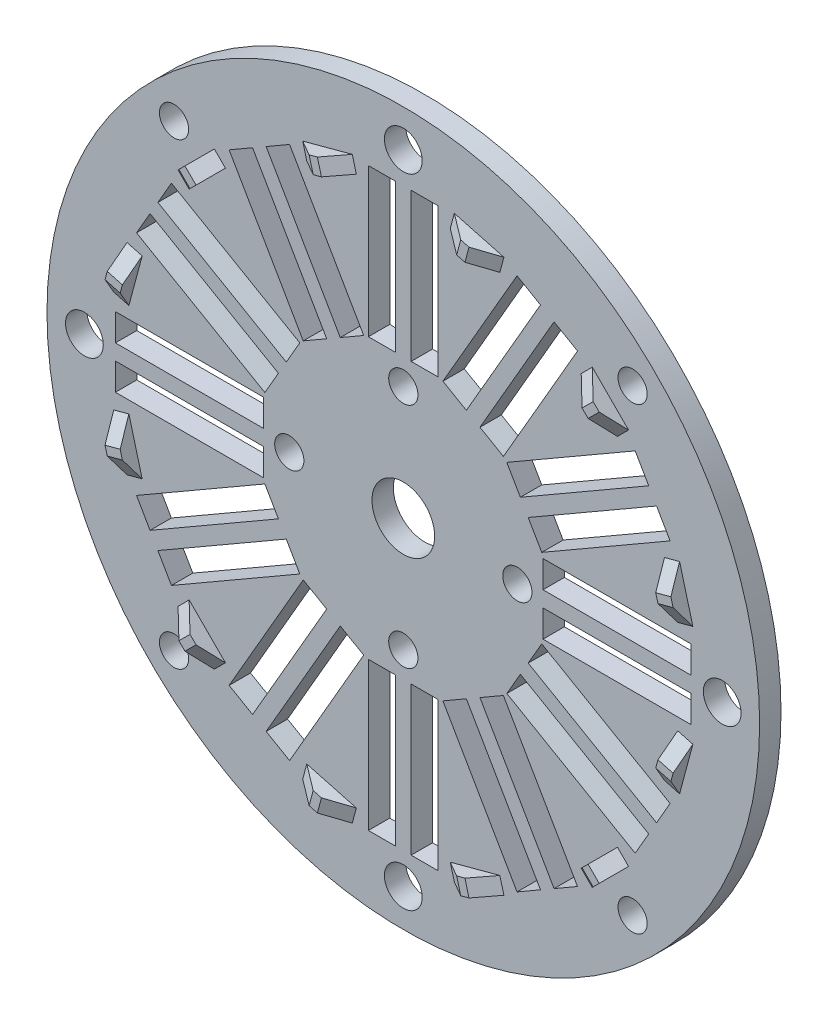
SolidWorks part; units mm, degrees
ref_plane "Alzado" through (0, 0, 0) normal (1, 0, 0) x (0, 1, 0)
ref_plane "Planta" through (0, 0, 0) normal (0, 0, 1) x (0, 1, 0)
ref_plane "Vista lateral" through (0, 0, 0) normal (0, 1, 0) x (-1, 0, 0)
sketch "Croquis1" plane through (0, 0, 0) normal (0, 0, 1) x (0, 1, 0)
  circle A0 centre (0, 0) radius 50
  dimension "D1" = 100
extrude "Saliente-Extruir1" add sketch "Croquis1" along normal blind 3
sketch "Croquis2" plane through (0, 0, 3) normal (0, 0, 1) x (1, 0, 0)
  line L102 (15.9565, 37.4374) -> (5.5565, 19.4241)
  line L103 (-4.9, 40.4) -> (4.9, 40.4)
  line L104 (-4.9, 40.4) -> (-4.9, 19.6)
  line L105 (-4.9, 19.6) -> (4.9, 19.6)
  line L106 (4.9, 40.4) -> (4.9, 19.6)
  line L107 (-4.9, 40.4) -> (4.9, 19.6) construction
  line L108 (-4.9, 19.6) -> (4.9, 40.4) construction
  line L109 (15.9565, 37.4374) -> (24.4435, 32.5374)
  line L110 (24.4435, 32.5374) -> (14.0435, 14.5241)
  line L111 (5.5565, 19.4241) -> (14.0435, 14.5241)
  line L112 (32.5374, 24.4435) -> (14.5241, 14.0435)
  line L113 (32.5374, 24.4435) -> (37.4374, 15.9565)
  line L114 (37.4374, 15.9565) -> (19.4241, 5.5565)
  line L115 (14.5241, 14.0435) -> (19.4241, 5.5565)
  line L116 (40.4, 4.9) -> (19.6, 4.9)
  line L117 (40.4, 4.9) -> (40.4, -4.9)
  line L118 (40.4, -4.9) -> (19.6, -4.9)
  line L119 (19.6, 4.9) -> (19.6, -4.9)
  line L120 (37.4374, -15.9565) -> (19.4241, -5.5565)
  line L121 (37.4374, -15.9565) -> (32.5374, -24.4435)
  line L122 (32.5374, -24.4435) -> (14.5241, -14.0435)
  line L123 (19.4241, -5.5565) -> (14.5241, -14.0435)
  line L124 (24.4435, -32.5374) -> (14.0435, -14.5241)
  line L125 (24.4435, -32.5374) -> (15.9565, -37.4374)
  line L126 (15.9565, -37.4374) -> (5.5565, -19.4241)
  line L127 (14.0435, -14.5241) -> (5.5565, -19.4241)
  line L128 (4.9, -40.4) -> (4.9, -19.6)
  line L129 (4.9, -40.4) -> (-4.9, -40.4)
  line L130 (-4.9, -40.4) -> (-4.9, -19.6)
  line L131 (4.9, -19.6) -> (-4.9, -19.6)
  line L132 (-15.9565, -37.4374) -> (-5.5565, -19.4241)
  line L133 (-15.9565, -37.4374) -> (-24.4435, -32.5374)
  line L135 (-24.4435, -32.5374) -> (-14.0435, -14.5241)
  line L136 (-5.5565, -19.4241) -> (-14.0435, -14.5241)
  line L180 (-32.5374, -24.4435) -> (-14.5241, -14.0435)
  line L181 (-32.5374, -24.4435) -> (-37.4374, -15.9565)
  line L182 (-37.4374, -15.9565) -> (-19.4241, -5.5565)
  line L183 (-14.5241, -14.0435) -> (-19.4241, -5.5565)
  line L184 (-40.4, -4.9) -> (-19.6, -4.9)
  line L185 (-40.4, -4.9) -> (-40.4, 4.9)
  line L186 (-40.4, 4.9) -> (-19.6, 4.9)
  line L187 (-19.6, -4.9) -> (-19.6, 4.9)
  line L188 (-37.4374, 15.9565) -> (-19.4241, 5.5565)
  line L189 (-37.4374, 15.9565) -> (-32.5374, 24.4435)
  line L190 (-32.5374, 24.4435) -> (-14.5241, 14.0435)
  line L191 (-19.4241, 5.5565) -> (-14.5241, 14.0435)
  line L192 (-24.4435, 32.5374) -> (-14.0435, 14.5241)
  line L193 (-24.4435, 32.5374) -> (-15.9565, 37.4374)
  line L194 (-15.9565, 37.4374) -> (-5.5565, 19.4241)
  line L195 (-14.0435, 14.5241) -> (-5.5565, 19.4241)
  point P0 (0, 30)
  point P51 (0, 0)
  dimension "D1" = 20.8
  dimension "D2" = 9.8
  dimension "D3" = 0
  dimension "D4" = 30
  dimension "D5" = 12
extrude "Cortar-Extruir1" cut sketch "Croquis2" against normal through all
sketch "Croquis3" plane through (0, 0, 3) normal (0, 0, 1) x (1, 0, 0)
  line L5 (19.2474, 35.5374) -> (8.8474, 17.5241)
  line L6 (-1.1, 40.4) -> (1.1, 40.4)
  line L51 (-1.1, 40.4) -> (-1.1, 19.6)
  line L52 (-1.1, 19.6) -> (1.1, 19.6)
  line L53 (1.1, 40.4) -> (1.1, 19.6)
  line L54 (-1.1, 40.4) -> (1.1, 19.6) construction
  line L55 (-1.1, 19.6) -> (1.1, 40.4) construction
  line L56 (19.2474, 35.5374) -> (21.1526, 34.4374)
  line L57 (21.1526, 34.4374) -> (10.7526, 16.4241)
  line L58 (8.8474, 17.5241) -> (10.7526, 16.4241)
  line L59 (34.4374, 21.1526) -> (16.4241, 10.7526)
  line L60 (34.4374, 21.1526) -> (35.5374, 19.2474)
  line L61 (35.5374, 19.2474) -> (17.5241, 8.8474)
  line L62 (16.4241, 10.7526) -> (17.5241, 8.8474)
  line L63 (40.4, 1.1) -> (19.6, 1.1)
  line L64 (40.4, 1.1) -> (40.4, -1.1)
  line L65 (40.4, -1.1) -> (19.6, -1.1)
  line L66 (19.6, 1.1) -> (19.6, -1.1)
  line L67 (35.5374, -19.2474) -> (17.5241, -8.8474)
  line L68 (35.5374, -19.2474) -> (34.4374, -21.1526)
  line L69 (34.4374, -21.1526) -> (16.4241, -10.7526)
  line L70 (17.5241, -8.8474) -> (16.4241, -10.7526)
  line L71 (21.1526, -34.4374) -> (10.7526, -16.4241)
  line L72 (21.1526, -34.4374) -> (19.2474, -35.5374)
  line L73 (19.2474, -35.5374) -> (8.8474, -17.5241)
  line L74 (10.7526, -16.4241) -> (8.8474, -17.5241)
  line L75 (1.1, -40.4) -> (1.1, -19.6)
  line L76 (1.1, -40.4) -> (-1.1, -40.4)
  line L77 (-1.1, -40.4) -> (-1.1, -19.6)
  line L78 (1.1, -19.6) -> (-1.1, -19.6)
  line L79 (-19.2474, -35.5374) -> (-8.8474, -17.5241)
  line L80 (-19.2474, -35.5374) -> (-21.1526, -34.4374)
  line L81 (-21.1526, -34.4374) -> (-10.7526, -16.4241)
  line L82 (-8.8474, -17.5241) -> (-10.7526, -16.4241)
  line L83 (-34.4374, -21.1526) -> (-16.4241, -10.7526)
  line L84 (-34.4374, -21.1526) -> (-35.5374, -19.2474)
  line L85 (-35.5374, -19.2474) -> (-17.5241, -8.8474)
  line L86 (-16.4241, -10.7526) -> (-17.5241, -8.8474)
  line L87 (-40.4, -1.1) -> (-19.6, -1.1)
  line L88 (-40.4, -1.1) -> (-40.4, 1.1)
  line L89 (-40.4, 1.1) -> (-19.6, 1.1)
  line L90 (-19.6, -1.1) -> (-19.6, 1.1)
  line L91 (-35.5374, 19.2474) -> (-17.5241, 8.8474)
  line L92 (-35.5374, 19.2474) -> (-34.4374, 21.1526)
  line L93 (-34.4374, 21.1526) -> (-16.4241, 10.7526)
  line L94 (-17.5241, 8.8474) -> (-16.4241, 10.7526)
  line L95 (-21.1526, 34.4374) -> (-10.7526, 16.4241)
  line L96 (-21.1526, 34.4374) -> (-19.2474, 35.5374)
  line L97 (-19.2474, 35.5374) -> (-8.8474, 17.5241)
  line L98 (-10.7526, 16.4241) -> (-8.8474, 17.5241)
  point P0 (0, 30)
  point P7 (15, 25.9808)
  point P13 (25.9808, 15)
  point P18 (30, 0)
  point P23 (25.9808, -15)
  point P28 (15, -25.9808)
  point P33 (0, -30)
  point P38 (-15, -25.9808)
  point P43 (-25.9808, -15)
  point P48 (-30, 0)
  point P53 (-25.9808, 15)
  point P59 (-15, 25.9808)
  point P64 (0, 0)
  dimension "D1" = 30
  dimension "D2" = 20.8
  dimension "D3" = 2.2
  dimension "D4" = 12
extrude "Saliente-Extruir2" add sketch "Croquis3" against normal blind 3
sketch "Croquis5" plane through (0, 0, 3) normal (0, 0, 1) x (1, 0, 0)
  circle A0 centre (0, 0) radius 4.4
  circle A1 centre (0, 44.75) radius 2.65
  circle A2 centre (44.75, 0) radius 2.65
  circle A3 centre (0, -44.75) radius 2.65
  circle A4 centre (-44.75, 0) radius 2.65
  point P19 (0, 0)
  dimension "D2" = 8.8
  dimension "D3" = 5.3
  dimension "D5" = 5.3
  dimension "D6" = 5.3
  dimension "D7" = 5.3
  dimension "D1" = 44.75
  dimension "D4" = 4
extrude "Cortar-Extruir3" cut sketch "Croquis5" against normal blind 10
sketch "Croquis6" plane through (0, 0, 3) normal (0, 0, 1) x (1, 0, 0)
  line L0 (0, 0) -> (28.2843, 28.2843) construction
  line L6 (26.5165, 31.6077) -> (31.6077, 26.5165)
  line L7 (26.5165, 31.6077) -> (24.9609, 30.052)
  line L52 (24.9609, 30.052) -> (30.052, 24.9609)
  line L53 (31.6077, 26.5165) -> (30.052, 24.9609)
  line L54 (26.5165, 31.6077) -> (30.052, 24.9609) construction
  line L55 (24.9609, 30.052) -> (31.6077, 26.5165) construction
  line L56 (38.7678, 14.1148) -> (36.6428, 13.5454)
  line L57 (38.7678, 14.1148) -> (40.6313, 7.1601)
  line L58 (40.6313, 7.1601) -> (38.5063, 6.5907)
  line L59 (36.6428, 13.5454) -> (38.5063, 6.5907)
  line L60 (36.6428, 13.5454) -> (40.6313, 7.1601) construction
  line L61 (38.7678, 14.1148) -> (38.5063, 6.5907) construction
  line L62 (40.6313, -7.1601) -> (38.5063, -6.5907)
  line L63 (40.6313, -7.1601) -> (38.7678, -14.1148)
  line L64 (38.7678, -14.1148) -> (36.6428, -13.5454)
  line L65 (38.5063, -6.5907) -> (36.6428, -13.5454)
  line L66 (38.5063, -6.5907) -> (38.7678, -14.1148) construction
  line L67 (40.6313, -7.1601) -> (36.6428, -13.5454) construction
  line L68 (31.6077, -26.5165) -> (30.052, -24.9609)
  line L69 (31.6077, -26.5165) -> (26.5165, -31.6077)
  line L70 (26.5165, -31.6077) -> (24.9609, -30.052)
  line L71 (30.052, -24.9609) -> (24.9609, -30.052)
  line L72 (30.052, -24.9609) -> (26.5165, -31.6077) construction
  line L73 (31.6077, -26.5165) -> (24.9609, -30.052) construction
  line L74 (14.1148, -38.7678) -> (13.5454, -36.6428)
  line L75 (14.1148, -38.7678) -> (7.1601, -40.6313)
  line L76 (7.1601, -40.6313) -> (6.5907, -38.5063)
  line L77 (13.5454, -36.6428) -> (6.5907, -38.5063)
  line L78 (13.5454, -36.6428) -> (7.1601, -40.6313) construction
  line L79 (14.1148, -38.7678) -> (6.5907, -38.5063) construction
  line L80 (-7.1601, -40.6313) -> (-6.5907, -38.5063)
  line L81 (-7.1601, -40.6313) -> (-14.1148, -38.7678)
  line L82 (-14.1148, -38.7678) -> (-13.5454, -36.6428)
  line L83 (-6.5907, -38.5063) -> (-13.5454, -36.6428)
  line L84 (-6.5907, -38.5063) -> (-14.1148, -38.7678) construction
  line L85 (-7.1601, -40.6313) -> (-13.5454, -36.6428) construction
  line L86 (-26.5165, -31.6077) -> (-24.9609, -30.052)
  line L87 (-26.5165, -31.6077) -> (-31.6077, -26.5165)
  line L88 (-31.6077, -26.5165) -> (-30.052, -24.9609)
  line L89 (-24.9609, -30.052) -> (-30.052, -24.9609)
  line L90 (-24.9609, -30.052) -> (-31.6077, -26.5165) construction
  line L91 (-26.5165, -31.6077) -> (-30.052, -24.9609) construction
  line L92 (-38.7678, -14.1148) -> (-36.6428, -13.5454)
  line L93 (-38.7678, -14.1148) -> (-40.6313, -7.1601)
  line L94 (-40.6313, -7.1601) -> (-38.5063, -6.5907)
  line L95 (-36.6428, -13.5454) -> (-38.5063, -6.5907)
  line L96 (-36.6428, -13.5454) -> (-40.6313, -7.1601) construction
  line L97 (-38.7678, -14.1148) -> (-38.5063, -6.5907) construction
  line L98 (-40.6313, 7.1601) -> (-38.5063, 6.5907)
  line L99 (-40.6313, 7.1601) -> (-38.7678, 14.1148)
  line L100 (-38.7678, 14.1148) -> (-36.6428, 13.5454)
  line L101 (-38.5063, 6.5907) -> (-36.6428, 13.5454)
  line L102 (-38.5063, 6.5907) -> (-38.7678, 14.1148) construction
  line L103 (-40.6313, 7.1601) -> (-36.6428, 13.5454) construction
  line L104 (-31.6077, 26.5165) -> (-30.052, 24.9609)
  line L105 (-31.6077, 26.5165) -> (-26.5165, 31.6077)
  line L106 (-26.5165, 31.6077) -> (-24.9609, 30.052)
  line L107 (-30.052, 24.9609) -> (-24.9609, 30.052)
  line L108 (-30.052, 24.9609) -> (-26.5165, 31.6077) construction
  line L109 (-31.6077, 26.5165) -> (-24.9609, 30.052) construction
  line L110 (-14.1148, 38.7678) -> (-13.5454, 36.6428)
  line L111 (-14.1148, 38.7678) -> (-7.1601, 40.6313)
  line L112 (-7.1601, 40.6313) -> (-6.5907, 38.5063)
  line L113 (-13.5454, 36.6428) -> (-6.5907, 38.5063)
  line L114 (-13.5454, 36.6428) -> (-7.1601, 40.6313) construction
  line L115 (-14.1148, 38.7678) -> (-6.5907, 38.5063) construction
  line L116 (7.1601, 40.6313) -> (6.5907, 38.5063)
  line L117 (7.1601, 40.6313) -> (14.1148, 38.7678)
  line L118 (14.1148, 38.7678) -> (13.5454, 36.6428)
  line L119 (6.5907, 38.5063) -> (13.5454, 36.6428)
  line L120 (6.5907, 38.5063) -> (14.1148, 38.7678) construction
  line L121 (7.1601, 40.6313) -> (13.5454, 36.6428) construction
  point P0 (28.2843, 28.2843)
  point P53 (0, 0)
  dimension "D1" = 7.2
  dimension "D2" = 2.2
extrude "Saliente-Extruir3" add sketch "Croquis6" along normal blind 2
chamfer "Chaflán1" distance 2 distance2 3 12 edges at (6.8754, -39.5688, 5) (-30.8299, -25.7387, 5) (-13.8301, -37.7053, 5) (25.7387, -30.8299, 5) (37.7053, -13.8301, 5) (39.5688, 6.8754, 5) (-39.5688, -6.8754, 5) (-37.7053, 13.8301, 5) (-25.7387, 30.8299, 5) (-6.8754, 39.5688, 5) (13.8301, 37.7053, 5) (30.8299, 25.7387, 5) first distance on face at (6.8754, -39.5688, 4) first distance on face at (-30.8299, -25.7387, 4) first distance on face at (-13.8301, -37.7053, 4) first distance on face at (25.7387, -30.8299, 4) first distance on face at (37.7053, -13.8301, 4) first distance on face at (39.5688, 6.8754, 4) first distance on face at (-39.5688, -6.8754, 4) first distance on face at (-37.7053, 13.8301, 4) first distance on face at (-25.7387, 30.8299, 4) first distance on face at (-6.8754, 39.5688, 4) first distance on face at (13.8301, 37.7053, 4) first distance on face at (30.8299, 25.7387, 4)
chamfer "Chaflán2" distance 2 distance2 3 12 edges at (-37.7053, -13.8301, 5) (-25.7387, -30.8299, 5) (-6.8754, -39.5688, 5) (13.8301, -37.7053, 5) (30.8299, -25.7387, 5) (39.5688, -6.8754, 5) (-39.5688, 6.8754, 5) (37.7053, 13.8301, 5) (25.7387, 30.8299, 5) (6.8754, 39.5688, 5) (-13.8301, 37.7053, 5) (-30.8299, 25.7387, 5) first distance on face at (-37.7053, -13.8301, 4) first distance on face at (-25.7387, -30.8299, 4) first distance on face at (-6.8754, -39.5688, 4) first distance on face at (13.8301, -37.7053, 4) first distance on face at (30.8299, -25.7387, 4) first distance on face at (39.5688, -6.8754, 4) first distance on face at (-39.5688, 6.8754, 4) first distance on face at (37.7053, 13.8301, 4) first distance on face at (25.7387, 30.8299, 4) first distance on face at (6.8754, 39.5688, 4) first distance on face at (-13.8301, 37.7053, 4) first distance on face at (-30.8299, 25.7387, 4)
sketch "Croquis7" plane through (0, 0, 3) normal (0, 0, 1) x (1, 0, 0)
  circle A0 centre (0, 16) radius 2.05
  circle A1 centre (16, 0) radius 2.05
  circle A2 centre (0, -16) radius 2.05
  circle A3 centre (-16, 0) radius 2.05
  circle A4 centre (-32.1734, 32.1734) radius 2.05
  circle A5 centre (32.1734, 32.1734) radius 2.05
  circle A6 centre (32.1734, -32.1734) radius 2.05
  circle A7 centre (-32.1734, -32.1734) radius 2.05
  point P12 (0, 0)
  point P21 (0, 0)
  dimension "D1" = 4.1
  dimension "D4" = 4.1
  dimension "D2" = 16
  dimension "D5" = 45.5
  dimension "D3" = 4
  dimension "D6" = 4
extrude "Cortar-Extruir4" cut sketch "Croquis7" against normal through all
cosmetic thread "Rosca cosmética1"
cosmetic thread "Rosca cosmética2"
cosmetic thread "Rosca cosmética3"
cosmetic thread "Rosca cosmética4"
cosmetic thread "Rosca cosmética5"
cosmetic thread "Rosca cosmética6"
cosmetic thread "Rosca cosmética7"
cosmetic thread "Rosca cosmética8"
